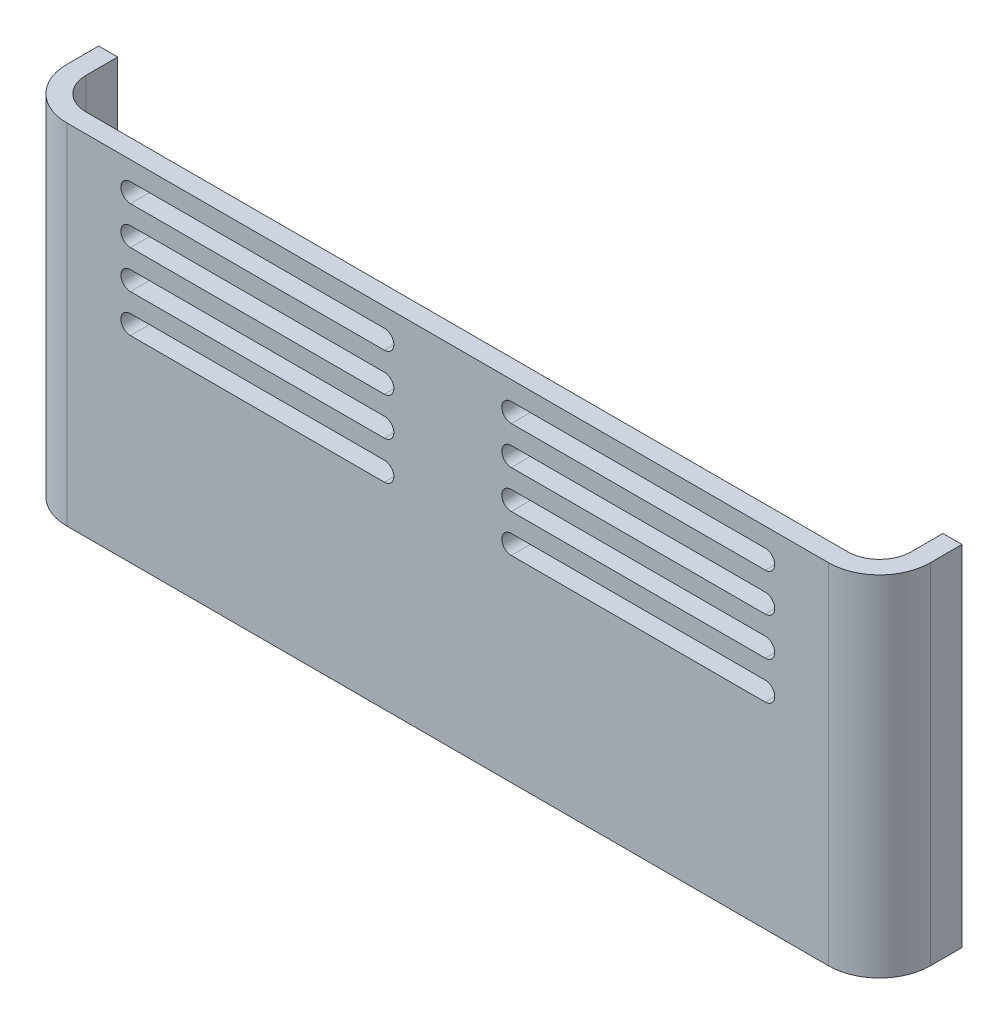
SolidWorks part; units mm, degrees
ref_plane "Front Plane" through (0, 0, 0) normal (0, 0, 1) x (1, 0, 0)
ref_plane "Top Plane" through (0, 0, 0) normal (0, 1, 0) x (1, 0, 0)
ref_plane "Right Plane" through (0, 0, 0) normal (1, 0, 0) x (0, 0, -1)
sketch "Sketch1" plane through (0, 0, 0) normal (0, 1, 0) x (1, 0, 0)
  line L0 (-3, 5) -> (-3, 10)
  line L1 (5, 0) -> (125, 0)
  line L2 (0, 5) -> (0, 10)
  line L4 (130, 5) -> (130, 10)
  line L5 (5, -3) -> (125, -3)
  line L6 (133, 5) -> (133, 10)
  line L7 (-3, 10) -> (0, 10)
  line L8 (130, 10) -> (133, 10)
  arc A0 (0, 5) -> (5, 0) centre (5, 5) ccw
  arc A1 (130, 5) -> (125, 0) centre (125, 5) cw
  arc A2 (-3, 5) -> (5, -3) centre (5, 5) ccw
  arc A3 (133, 5) -> (125, -3) centre (125, 5) cw
  point P7 (0, 0)
  point P10 (130, 0)
  dimension "D3" = 5
  dimension "D4" = 5
  dimension "D1" = 130
  dimension "D2" = 10
  dimension "D5" = 3
extrude "Boss-Extrude1" add sketch "Sketch1" along normal blind 55 contours L0 L7 L2 A0 L1 A1 L4 L8 L6 A3 L5 A2
sketch "Sketch2" plane through (0, 0, 0) normal (0, 1, 0) x (1, 0, 0)
  line L0 (0, 10) -> (5, 10)
  line L1 (10, 5) -> (10, 0)
  line L2 (0, 10) -> (0, 5)
  line L4 (10, 0) -> (5, 0)
  line L6 (65, 0) -> (65, 22.727)
  line L7 (5, 0) -> (125, 0) construction
  line L8 (120, 0) -> (125, 0)
  line L9 (130, 10) -> (130, 5)
  line L10 (120, 5) -> (120, 0)
  line L11 (130, 10) -> (125, 10)
  circle A0 centre (5, 5) radius 5
  circle A1 centre (5, 5) radius 2.75
  circle A2 centre (125, 5) radius 2.75
  circle A3 centre (125, 5) radius 5
  dimension "D1" = 5.5
  dimension "D2" = 10
extrude "Boss-Extrude2" add sketch "Sketch2" along normal blind 6 from offset 15 contours A0 L0 L2 | A0 A1 | A0 L4 L1 | L8 A3 L10 | A3 A2 | A2 | L11 A3 L9 | A1 region at (1.1168, 0, -8.8832) region at (8.4355, 0, -8.4355) region at (8.8832, 0, -1.1168) region at (121.1168, 0, -1.1168) region at (121.5645, 0, -1.5645) region at (128.8832, 0, -8.8832) region at (5, 0, -5) region at (125, 0, -5)
extrude "Cut-Extrude1" cut sketch "Sketch2<4>" along normal blind 4 from surface contours A1 | A2 region at (5, 0, -5) region at (125, 0, -5) starting at face at (5, 15, -5)
sketch "Sketch2<4>" plane through (0, 0, 0) normal (0, 1, 0) x (1, 0, 0) same geometry as "Sketch2"
sketch "Sketch3" plane through (0, 0, 0) normal (0, 0, 1) x (1, 0, 0)
  line L0 (65, 55) -> (65, 35.1237)
  line L1 (5, 55) -> (125, 55) construction
  line L2 (15, 43) -> (55, 43)
  line L3 (15, 52) -> (55, 52)
  line L4 (15, 52) -> (15, 49)
  line L5 (15, 49) -> (55, 49)
  line L6 (55, 52) -> (55, 49)
  line L7 (15, 46) -> (55, 46)
  line L8 (15, 37) -> (55, 37)
  line L9 (15, 40) -> (55, 40)
  line L10 (115, 40) -> (75, 40)
  line L11 (115, 37) -> (75, 37)
  line L12 (115, 46) -> (75, 46)
  line L13 (75, 52) -> (75, 49)
  line L14 (115, 49) -> (75, 49)
  line L15 (115, 52) -> (115, 49)
  line L16 (115, 52) -> (75, 52)
  line L17 (115, 43) -> (75, 43)
  line L18 (15, 34) -> (55, 34)
  line L19 (15, 31) -> (55, 31)
  line L20 (115, 31) -> (75, 31)
  line L21 (115, 34) -> (75, 34)
  arc A0 (15, 49) -> (15, 52) centre (15, 50.5) cw
  arc A1 (55, 52) -> (55, 49) centre (55, 50.5) cw
  arc A2 (15, 43) -> (15, 46) centre (15, 44.5) cw
  arc A3 (55, 46) -> (55, 43) centre (55, 44.5) cw
  arc A4 (15, 37) -> (15, 40) centre (15, 38.5) cw
  arc A5 (55, 40) -> (55, 37) centre (55, 38.5) cw
  arc A6 (75, 40) -> (75, 37) centre (75, 38.5) ccw
  arc A7 (115, 37) -> (115, 40) centre (115, 38.5) ccw
  arc A8 (75, 46) -> (75, 43) centre (75, 44.5) ccw
  arc A9 (115, 43) -> (115, 46) centre (115, 44.5) ccw
  arc A10 (75, 52) -> (75, 49) centre (75, 50.5) ccw
  arc A11 (115, 49) -> (115, 52) centre (115, 50.5) ccw
  arc A12 (15, 31) -> (15, 34) centre (15, 32.5) cw
  arc A13 (55, 34) -> (55, 31) centre (55, 32.5) cw
  arc A14 (75, 34) -> (75, 31) centre (75, 32.5) ccw
  arc A15 (115, 31) -> (115, 34) centre (115, 32.5) ccw
  point P10 (35, 52)
  dimension "D1" = 3
  dimension "D2" = 40
  dimension "D3" = 3
  dimension "D4" = 30
  dimension "D5" = 3
  dimension "D6" = 2
extrude "Cut-Extrude2" cut sketch "Sketch3" along normal blind 10 contours A5 L9 A4 L8 | A3 L7 A2 L2 | L11 A7 L10 A6 | L17 A9 L12 A8 | L15 L16 L13 L14 | L6 L3 L4 L5 | A0 L4 | A1 L6 | L13 A10 | L15 A11 | A13 L18 A12 L19 | L20 A15 L21 A14 region at (35, 44.5, 0) region at (35, 50.5, 0) region at (14.3634, 50.5, 0) region at (55.6366, 50.5, 0) region at (35, 38.5, 0) region at (95, 38.5, 0) region at (95, 44.5, 0) region at (95, 50.5, 0) region at (74.3634, 50.5, 0) region at (115.6366, 50.5, 0) region at (35, 32.5, 0) region at (95, 32.5, 0)
extrude "Boss-Extrude3" add sketch "Sketch2<5>" along normal blind 1 from surface contours A1 | A2 region at (5, 0, -5) region at (125, 0, -5) starting at face at (125, 15, -2.25)
sketch "Sketch2<5>" plane through (0, 0, 0) normal (0, 1, 0) x (1, 0, 0) same geometry as "Sketch2"
